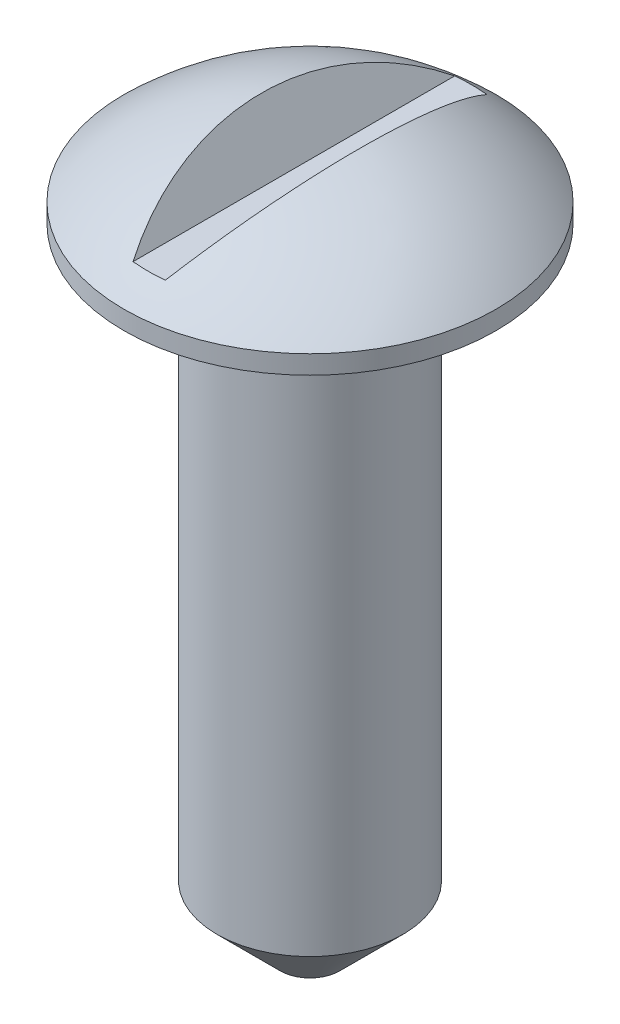
SolidWorks part; units mm, degrees
ref_plane "Front Plane" through (0, 0, 0) normal (0, 0, 1) x (1, 0, 0)
ref_plane "Top Plane" through (0, 0, 0) normal (0, 1, 0) x (1, 0, 0)
ref_plane "Right Plane" through (0, 0, 0) normal (1, 0, 0) x (0, 0, -1)
sketch "Sketch1" plane through (0, 0, 0) normal (0, 0, 1) x (1, 0, 0)
  line L0 (0, 0) -> (-250, 0)
  line L1 (-250, 0) -> (-250, 1700)
  line L2 (-250, 1700) -> (-500, 1700)
  line L3 (-500, 1700) -> (-500, 1750)
  line L4 (-500, 1750) -> (0, 1750)
  line L5 (0, 1750) -> (0, 0)
  line L6 (0, 0) -> (0, -317.1964) construction
  dimension "D1" = 500
  dimension "D2" = 1000
  dimension "D3" = 1700
  dimension "D4" = 50
revolve "Revolve1" add sketch "Sketch1" angle 360 about L6
dome "Dome1" faces to dome 1 distance 200 reverse direction no elliptical dome no face at (0, 1750, 500) parameters "D1"=200
sketch "Sketch2" plane through (0, 0, 0) normal (0, 0, 1) x (1, 0, 0)
  line L0 (0, 0) -> (0, 2476.9469) construction
  line L1 (-130.5292, 1938.1529) -> (-43.2964, 1805.4227)
  line L2 (-43.2964, 1805.4227) -> (43.2964, 1805.4227)
  line L3 (130.5292, 1938.1529) -> (43.2964, 1805.4227)
  arc A0 (500, 1750) -> (-500, 1750) centre (0, 1225) ccw construction
  point P10 (0, 1805.4227)
extrude "Cut-Extrude1" cut sketch "Sketch2" along normal through all and the other way through all flip side to cut
chamfer "Chamfer5" distance 170 angle 45 1 edges at (0, 0, 250)
